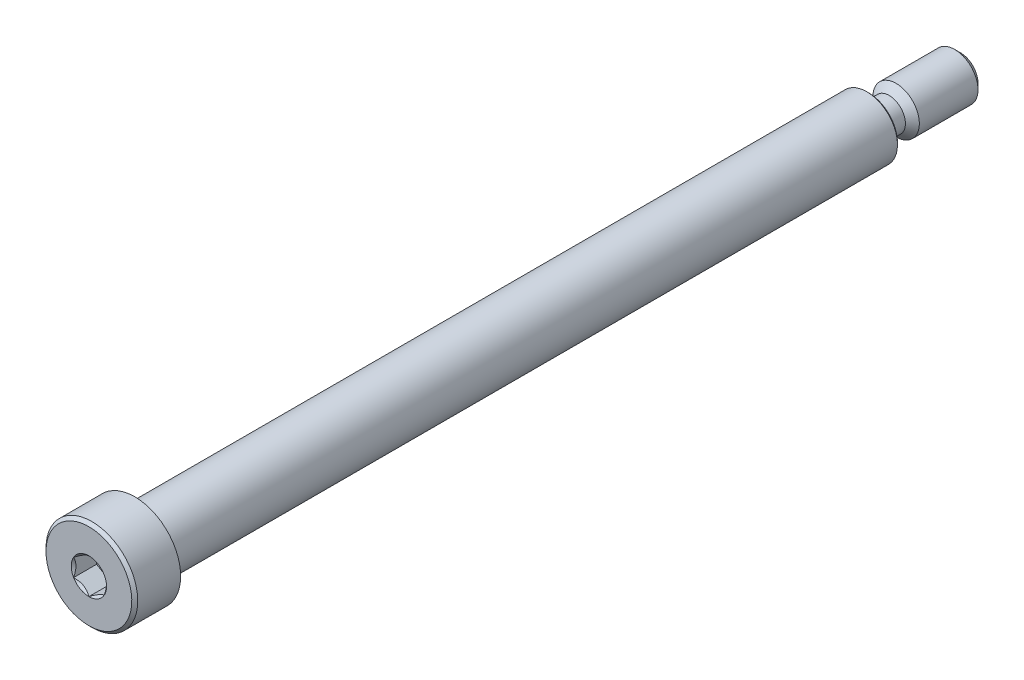
SolidWorks part; units mm, degrees
material "Alloy Steel"
ref_plane "Front" through (0, 0, 0) normal (0, 0, 1) x (1, 0, 0)
ref_plane "Top" through (0, 0, 0) normal (0, 1, 0) x (1, 0, 0)
ref_plane "Right" through (0, 0, 0) normal (1, 0, 0) x (0, 0, -1)
sketch "Sketch1" plane through (0, 0, 0) normal (1, 0, 0) x (0, 0, -1)
  line L0 (0, 4.7625) -> (4.7625, 4.7625)
  line L1 (4.7625, 4.7625) -> (4.7625, 3.175)
  line L2 (4.7625, 3.175) -> (80.9625, 3.175)
  line L3 (80.9625, 3.175) -> (80.9625, 2.413)
  line L4 (80.9625, 2.413) -> (90.4875, 2.413)
  line L5 (90.4875, 2.413) -> (90.4875, 0)
  line L6 (90.4875, 0) -> (0, 0)
  line L7 (0, 0) -> (0, 4.7625)
  line L8 (0, 4.7625) -> (0, -4.7625) construction
  line L9 (90.4875, 2.413) -> (90.4875, -2.413) construction
  line L10 (80.9625, 3.175) -> (80.9625, -3.175) construction
  line L11 (90.4875, -2.413) -> (88.8097, -2.413) construction
  line L12 (42.8625, 0) -> (42.8625, 3.175) construction
  point P8 (88.9, -2.413)
  point P12 (80.9625, 0)
  point P17 (12.3825, 3.175)
  point P18 (42.8625, 0)
  point P19 (42.8625, 3.175)
  point P20 (73.3425, 3.175)
  point P21 (73.3425, -3.175)
  point P22 (12.3825, -3.175)
  dimension "Head Dia" = 9.525
  dimension "Head Ht" = 4.7625
  dimension "Thread Lg" = 9.525
  dimension "Thread Dia" = 4.826
  dimension "Shoulder Dia" = 6.35
  dimension "Shoulder Lg" = 76.2
  dimension "D1" = 1.5875
  dimension "D2" = 1.6778
  dimension "D3" = 38.1
  dimension "D4" = 7.62
revolve "Revolve1" add sketch "Sketch1" angle 360 mid plane about L6
ref_plane "Plane1" through (0, 0, -90.4875) normal (0, 0, 1) x (1, 0, 0)
sketch "Sketch3" [suppressed] plane through (0, 0, -90.4875) normal (0, 0, 1) x (1, 0, 0)
  circle A0 centre (0, 0) radius 2.413
sketch "Sketch5" plane through (0, 0, 0) normal (1, 0, 0) x (0, 0, -1)
  line L0 (80.9625, 3.175) -> (84.5566, 3.175)
  line L1 (84.5566, 3.175) -> (83.0707, 1.6891)
  line L2 (83.0707, 1.6891) -> (81.6864, 1.6891)
  line L3 (80.9625, 3.175) -> (80.9625, 2.413)
  line L5 (80.9625, 2.413) -> (90.4875, 2.413) construction
  line L6 (90.4875, 0) -> (83.0707, 0) construction
  line L7 (86.7791, 0) -> (86.7791, -2.413) construction
  arc A0 (80.9625, 2.413) -> (81.6864, 1.6891) centre (81.6864, 2.413) ccw
  dimension "D1" = 45
  dimension "CADB" = 2.1082
  dimension "CADA" = 3.3782
revolve "Cut-Revolve1" cut sketch "Sketch5" angle 360 mid plane about L6
chamfer "Chamfer1" distance 0.6032 angle 45 1 edges at (0, 2.413, -90.4875)
chamfer "Chamfer2" distance 0.3096 angle 45 1 edges at (0, 4.7625, 0)
chamfer "Chamfer3" distance 0.2032 angle 45 1 edges at (0, 3.175, -80.9625)
sketch "Sketch10" plane through (0, 0, 0) normal (1, 0, 0) x (0, 0, -1)
  line L0 (0.3096, 0) -> (4.4529, 0) construction
  line L1 (0.3096, -4.7625) -> (0.3096, 4.7625) construction
  line L3 (0.3096, 0) -> (0, 0) construction
  line L4 (4.4529, 0) -> (4.7625, 0) construction
  line L5 (4.7625, -4.7625) -> (4.7625, 4.7625) construction
  point P6 (2.3813, 0)
  dimension "D1" = 4.1434
ref_plane "Plane2" through (0, 0, -2.3813) normal (0, 0, 1) x (1, 0, 0)
sketch "Sketch11" plane through (0, 0, -2.3813) normal (0, 0, 1) x (1, 0, 0)
  line L0 (0, 4.5148) -> (0, 4.7625) construction
  line L1 (0, 4.5148) -> (0.143, 4.7625)
  line L2 (0, 4.5148) -> (-0.143, 4.7625)
  line L3 (-0.143, 4.7625) -> (0.143, 4.7625)
  line L4 (0, 0) -> (-0.143, 4.7625) construction
  line L5 (0.143, 4.7625) -> (0, 0) construction
  circle A1 centre (0, 0) radius 4.7625 construction
  circle A2 centre (0, 0) radius 4.5148 construction
  circle A3 centre (0, 0) radius 4.4529 construction
  point P3 (0, 0.0018)
  point P8 (2.3908, 0.7309)
  dimension "D1" = 0.2476
  dimension "D2" = 3.439
extrude "Cut-Extrude5" [suppressed] cut sketch "Sketch11" against normal mid plane 3.9362
pattern_circular "CirPattern1" [suppressed] count 99 over 360 of bodies 119
sketch "Sketch8" plane through (0, 0, 0) normal (0, 0, 1) x (1, 0, 0)
  line L1 (1.5875, 0.9165) -> (0, 1.8331)
  line L2 (0, 1.8331) -> (-1.5875, 0.9165)
  line L3 (-1.5875, 0.9165) -> (-1.5875, -0.9165)
  line L4 (-1.5875, -0.9165) -> (0, -1.8331)
  line L5 (0, -1.8331) -> (1.5875, -0.9165)
  line L6 (1.5875, -0.9165) -> (1.5875, 0.9165)
  circle A0 centre (0, 0) radius 1.5875 construction
  dimension "Hex" = 3.175
extrude "Cut-Extrude2" cut sketch "Sketch8" against normal blind 2.3813
sketch "Sketch9" plane through (0, 0, 0) normal (0, 0, 1) x (1, 0, 0)
  circle A0 centre (0, 0) radius 1.8331
extrude "Cut-Extrude4" cut sketch "Sketch9" against normal blind 2.3813 draft 45
sketch "Front Sketch" plane through (0, 0, 0) normal (0, 0, 1) x (1, 0, 0)
  line L0 (1.5875, -0.9165) -> (1.5875, 0.9165) construction
  line L1 (-1.5875, 0.9165) -> (-1.5875, -0.9165) construction
  circle A0 centre (0, 0) radius 4.7625 construction
  point P4 (-1.5875, 0)
  point P5 (1.5875, 0)
  point P6 (4.7625, 0)
  point P9 (-4.7625, 0)
ref_plane "Contact Plane 1" [suppressed] through (0, 0, -4.7625) normal (0, 0, -1) x (-1, 0, 0)
ref_axis "Center Axis 1" [suppressed] through (0, 0, -90.4875) along (0, 0, 1)
curve "Helix/Spiral1" [suppressed] pitch 1.0583 height 10.5833 turns 10
sketch "Sketch4" [suppressed] plane through (0, 0, 0) normal (1, 0, 0) x (0, 0, -1)
  line L0 (90.4214, 2.5276) -> (91.4797, 2.5276) construction
  line L1 (91.4797, 2.5276) -> (90.9505, 1.611) construction
  line L3 (90.9505, 1.611) -> (90.4214, 2.5276) construction
  line L4 (90.4544, 2.4703) -> (91.4466, 2.4703) construction
  line L5 (90.4875, 2.413) -> (91.4135, 2.413) construction
  line L6 (90.8844, 1.7256) -> (91.0167, 1.7256) construction
  line L7 (90.9505, 1.7256) -> (90.9505, 1.611) construction
  line L8 (90.9505, 2.5276) -> (90.9505, 2.413) construction
  line L9 (90.4544, 2.4703) -> (91.4466, 2.4703)
  line L10 (91.4466, 2.4703) -> (91.0167, 1.7256)
  line L11 (91.0167, 1.7256) -> (90.8844, 1.7256)
  line L12 (90.8844, 1.7256) -> (90.4544, 2.4703)
  point P14 (90.9505, 2.4703)
  point P15 (90.9505, 2.5276)
  dimension "D1" = 1.0583
  dimension "D2" = 0.1323
sweep "Cut-Sweep1" [suppressed] cut profiles "Sketch4" path "Helix/Spiral1"
sketch "Sketch12" [suppressed] plane through (0, 0, 0) normal (1, 0, 0) x (0, 0, -1)
  line L1 (80.9625, 2.9718) -> (80.7593, 3.175)
  line L2 (80.7593, 3.175) -> (4.7625, 3.175)
  line L3 (4.7625, 3.175) -> (4.7625, 0)
  line L4 (4.7625, -4.7625) -> (4.7625, 4.7625) construction
  line L5 (4.7625, 0) -> (80.9625, 0)
  line L6 (80.9625, 2.9718) -> (80.9625, 2.413)
  line L7 (83.0707, 1.6891) -> (81.6864, 1.6891) construction
  line L8 (83.0707, 1.6891) -> (81.6864, 1.6891)
  line L9 (83.0707, 1.6891) -> (83.0707, 0)
  line L10 (83.0707, 0) -> (80.9625, 0)
  arc A0 (80.9625, 2.413) -> (81.6864, 1.6891) centre (81.6864, 2.413) ccw construction
  arc A1 (80.9625, 2.413) -> (81.6864, 1.6891) centre (81.6864, 2.413) ccw
revolve "Revolve2" [suppressed] add sketch "Sketch12" angle 360 about L5
equation "\"D3@Helix/Spiral1\" = \"Thread Lg@Sketch1\" + \"D4@Helix/Spiral1\""
equation "\"D1@Chamfer1\" = \"Thread Dia@Sketch1\" * .125"
equation "\"D1@Cut-Extrude2\"= \"Head Ht@Sketch1\" * .5"
equation "\"D1@Cut-Extrude4\" = \"D1@Cut-Extrude2\""
equation "\"D1@Chamfer2\" = \"Head Dia@Sketch1\" * .0325"
equation "\"D1@Sketch1\"=\"D4@Helix/Spiral1\"*1.5"
equation "\"D1@Sketch11\"=\"D1@Chamfer2\"*.8"
equation "\"D1@Cut-Extrude5\"=\"D1@Sketch10\"*.95"
equation "\"D1@CirPattern1\"=(360/\"D2@Sketch11\")-6"
equation "\"D3@Sketch1\"=\"Shoulder Lg@Sketch1\"/2"
equation "\"D4@Sketch1\"=\"D3@Sketch1\"*.2"
equation "\"D1@Sketch4\"=\"D4@Helix/Spiral1\""
equation "\"D2@Sketch4\"=\"D1@Sketch4\"/8"
